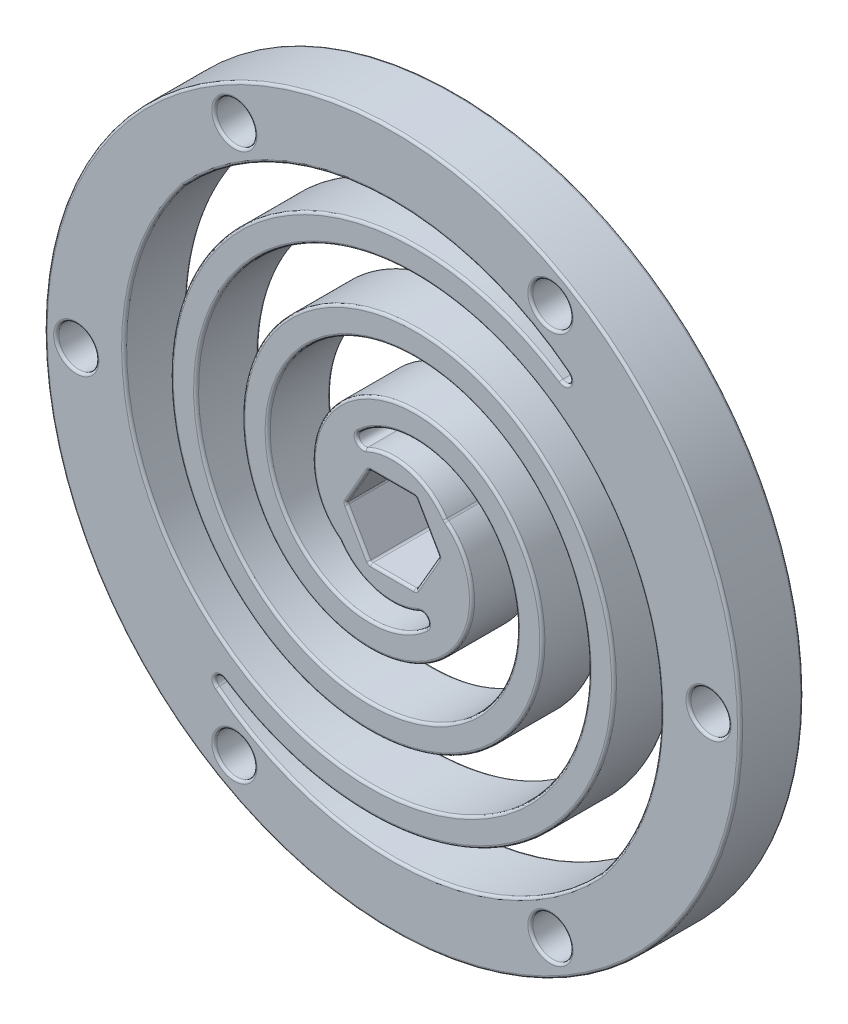
SolidWorks part; units mm, degrees
ref_plane "Front Plane" through (0, 0, 0) normal (0, 0, 1) x (1, 0, 0)
ref_plane "Top Plane" through (0, 0, 0) normal (0, 1, 0) x (1, 0, 0)
ref_plane "Right Plane" through (0, 0, 0) normal (1, 0, 0) x (0, 0, -1)
sketch "Sketch2" plane through (0, 0, 0) normal (0, 0, 1) x (1, 0, 0)
  line L0 (0, 0) -> (27.5, 0) construction
  line L1 (3.6662, 0) -> (1.8331, 3.175)
  line L2 (1.8331, 3.175) -> (-1.8331, 3.175)
  line L3 (-1.8331, 3.175) -> (-3.6662, 0)
  line L4 (-3.6662, 0) -> (-1.8331, -3.175)
  line L5 (-1.8331, -3.175) -> (1.8331, -3.175)
  line L6 (1.8331, -3.175) -> (3.6662, 0)
  line L7 (0, 0) -> (3.6662, 0) construction
  circle A0 centre (0, 0) radius 27.5
  circle A1 centre (0, 0) radius 22.5
  circle A2 centre (0, 0) radius 25 construction
  circle A3 centre (-25, 0) radius 1.5875
  circle A4 centre (0, 0) radius 5
  circle A5 centre (-12.5, 21.6506) radius 1.5875
  circle A6 centre (12.5, 21.6506) radius 1.5875
  circle A7 centre (25, 0) radius 1.5875
  circle A8 centre (12.5, -21.6506) radius 1.5875
  circle A9 centre (-12.5, -21.6506) radius 1.5875
  circle A10 centre (0, 0) radius 3.175 construction
  point P8 (0, 0)
  point P20 (0, 0)
  dimension "D1" = 50
  dimension "D2" = 55
  dimension "D3" = 45
  dimension "D4" = 3.175
  dimension "D5" = 10
  dimension "D7" = 6.35
  dimension "D8" = 0
  dimension "D6" = 6
sketch "Sketch3" plane through (0, 0, 0) normal (0, 0, 1) x (1, 0, 0)
  circle A0 centre (0, 0) radius 5
  circle A1 centre (0, 0) radius 5 construction
curve "Helix/Spiral1"
sketch "Sketch4" plane through (0, 0, 0) normal (0, 0, 1) x (1, 0, 0)
  line L1 (3.6662, 0) -> (1.8331, 3.175)
  line L2 (1.8331, 3.175) -> (-1.8331, 3.175)
  line L3 (-1.8331, 3.175) -> (-3.6662, 0)
  line L4 (-3.6662, 0) -> (-1.8331, -3.175)
  line L5 (-1.8331, -3.175) -> (1.8331, -3.175)
  line L6 (1.8331, -3.175) -> (3.6662, 0)
  circle A0 centre (0, 0) radius 27.5
  circle A1 centre (0, 0) radius 27.5 construction
  arc A2 (21.0974, 7.8198) -> (16.4884, -15.3096) centre (0, 0) ccw
  circle A3 centre (0, 0) radius 22.5 construction
  arc A4 (-4.1867, -2.7335) -> (-4.1828, 2.7394) centre (0, 0) ccw
  circle A5 centre (0, 0) radius 5 construction
  circle A6 centre (0, 0) radius 3.175 construction
  circle A7 centre (-25, 0) radius 1.5875
  circle A8 centre (-25, 0) radius 1.5875 construction
  circle A9 centre (-12.5, 21.6506) radius 1.5875
  circle A10 centre (12.5, 21.6506) radius 1.5875
  circle A11 centre (25, 0) radius 1.5875
  circle A12 centre (12.5, -21.6506) radius 1.5875
  circle A13 centre (-12.5, -21.6506) radius 1.5875
  spline S2 degree 3 poles (-921.9687, 1775.2435) (120.6606, -2.4111) (-4.8813, -17.0729) (-4.2797, 2.414) (-4.1558, 3.0013) (-3.6679, 4.1424) (-3.3002, 4.7041) (-2.3359, 5.6942) (-1.7333, 6.1283) (-0.3515, 6.7692) (0.4351, 6.979) (2.0951, 7.1004) (2.9764, 7.0121) (4.709, 6.5027) (5.5675, 6.0792) (7.1263, 4.9117) (7.8323, 4.163) (8.9643, 2.407) (9.394, 1.3934) (9.878, -0.7846) (9.9334, -1.956) (9.6158, -4.3077) (9.2415, -5.4949) (8.0664, -7.7186) (7.262, -8.761) (5.2882, -10.5401) (4.1135, -11.2809) (1.5171, -12.3274) (0.089, -12.6353) (-2.8511, -12.7334) (-4.3697, -12.5234) (-7.3011, -11.5652) (-8.72, -10.8146) (-11.2595, -8.8244) (-12.3849, -7.5806) (-14.1678, -4.7221) (-14.8283, -3.1019) (-15.559, 0.3326) (-15.6302, 2.1531) (-15.1274, 5.7722) (-14.552, 7.577) (-12.7805, 10.9347) (-11.581, 12.4931) (-8.6672, 15.1438) (-6.9482, 16.24) (-3.1749, 17.7964) (-1.1149, 18.2587) (3.1053, 18.4467) (5.2715, 18.1723) (9.4409, 16.8734) (11.4497, 15.8467) (15.0444, 13.1234) (16.6348, 11.4229) (19.1699, 7.5217) (20.1175, 5.3159) (21.2117, 0.6472) (21.3593, -1.8216) (20.7894, -6.7266) (20.0707, -9.1687) (17.8084, -13.7181) (16.2618, -15.8304) (12.4887, -19.443) (10.2578, -20.9468) (-48.904, -47.2318) (-226.7337, 148.1709) (1422.9512, 1363.8577) knots -1.044974 -1.044974 -1.044974 -1.044974 0.03125 0.03125 0.0625 0.0625 0.09375 0.09375 0.125 0.125 0.15625 0.15625 0.1875 0.1875 0.21875 0.21875 0.25 0.25 0.28125 0.28125 0.3125 0.3125 0.34375 0.34375 0.375 0.375 0.40625 0.40625 0.4375 0.4375 0.46875 0.46875 0.5 0.5 0.53125 0.53125 0.5625 0.5625 0.59375 0.59375 0.625 0.625 0.65625 0.65625 0.6875 0.6875 0.71875 0.71875 0.75 0.75 0.78125 0.78125 0.8125 0.8125 0.84375 0.84375 0.875 0.875 0.90625 0.90625 0.9375 0.9375 0.96875 0.96875 1.691459 1.691459 1.691459 1.691459 only from (-4.0603, 0.3419) to (-0.0726, -24.0026)
  spline S3 degree 3 poles (-4.1828, 2.7394) (-4.1195, 3.0167) (-4.0297, 3.2962) (-3.6679, 4.1424) (-3.3002, 4.7041) (-2.3359, 5.6942) (-1.7333, 6.1283) (-0.3515, 6.7692) (0.4351, 6.979) (2.0951, 7.1004) (2.9764, 7.0121) (4.709, 6.5027) (5.5675, 6.0792) (7.1263, 4.9117) (7.8323, 4.163) (8.9643, 2.407) (9.394, 1.3934) (9.878, -0.7846) (9.9334, -1.956) (9.6158, -4.3077) (9.2415, -5.4949) (8.0664, -7.7186) (7.262, -8.761) (5.2882, -10.5401) (4.1135, -11.2809) (1.5171, -12.3274) (0.089, -12.6353) (-2.8511, -12.7334) (-4.3697, -12.5234) (-7.3011, -11.5652) (-8.72, -10.8146) (-11.2595, -8.8244) (-12.3849, -7.5806) (-14.1678, -4.7221) (-14.8283, -3.1019) (-15.559, 0.3326) (-15.6302, 2.1531) (-15.1274, 5.7722) (-14.552, 7.577) (-12.7805, 10.9347) (-11.581, 12.4931) (-8.6672, 15.1438) (-6.9482, 16.24) (-3.1749, 17.7964) (-1.1149, 18.2587) (3.1053, 18.4467) (5.2715, 18.1723) (9.4409, 16.8734) (11.4497, 15.8467) (15.0444, 13.1234) (16.6348, 11.4229) (19.1699, 7.5217) (20.1175, 5.3159) (21.2117, 0.6472) (21.3593, -1.8216) (20.7894, -6.7266) (20.0707, -9.1687) (18.2649, -12.8) (17.4425, -14.0989) (16.4884, -15.3096) knots 0.047404 0.047404 0.047404 0.047404 0.0625 0.0625 0.09375 0.09375 0.125 0.125 0.15625 0.15625 0.1875 0.1875 0.21875 0.21875 0.25 0.25 0.28125 0.28125 0.3125 0.3125 0.34375 0.34375 0.375 0.375 0.40625 0.40625 0.4375 0.4375 0.46875 0.46875 0.5 0.5 0.53125 0.53125 0.5625 0.5625 0.59375 0.59375 0.625 0.625 0.65625 0.65625 0.6875 0.6875 0.71875 0.71875 0.75 0.75 0.78125 0.78125 0.8125 0.8125 0.84375 0.84375 0.875 0.875 0.90625 0.90625 0.924888 0.924888 0.924888 0.924888
  spline S4 degree 3 poles (-701.7537, 1870.0142) (184.6387, -12.0204) (-7.1764, -26.603) (-6.2709, 2.7296) (-6.093, 3.5576) (-5.4086, 5.1586) (-4.9053, 5.9226) (-3.5964, 7.2666) (-2.7968, 7.8397) (-0.9711, 8.6865) (0.0471, 8.956) (2.1915, 9.1128) (3.3089, 8.9989) (5.5046, 8.3535) (6.5743, 7.8239) (8.5175, 6.3686) (9.3837, 5.4476) (10.7748, 3.2897) (11.2948, 2.0598) (11.882, -0.5833) (11.9472, -1.9883) (11.566, -4.8107) (11.1205, -6.2199) (9.724, -8.8624) (8.7766, -10.0884) (6.4517, -12.1839) (5.08, -13.0477) (2.0459, -14.2706) (0.391, -14.6263) (-3.0198, -14.7401) (-4.7676, -14.4975) (-8.146, -13.3932) (-9.7689, -12.5337) (-12.678, -10.2537) (-13.9577, -8.838) (-15.9889, -5.5815) (-16.7357, -3.7473) (-17.564, 0.1456) (-17.6434, 2.1964) (-17.0761, 6.2794) (-16.4301, 8.3033) (-14.4402, 12.0749) (-13.0998, 13.8152) (-9.8402, 16.7805) (-7.9268, 17.9998) (-3.7216, 19.7344) (-1.4371, 20.2463) (3.2495, 20.4551) (5.6436, 20.1512) (10.2586, 18.7135) (12.4715, 17.5817) (16.438, 14.5767) (18.1847, 12.7081) (20.9739, 8.416) (22.0116, 5.9992) (23.2122, 0.8767) (23.3729, -1.8211) (22.7491, -7.1889) (21.9652, -9.8507) (19.4955, -14.8171) (17.8131, -17.1141) (13.7037, -21.0486) (11.2825, -22.6801) (-52.776, -51.1406) (-239.5534, 161.1192) (1378.94, 1402.9741) knots -1.077999 -1.077999 -1.077999 -1.077999 0.03125 0.03125 0.0625 0.0625 0.09375 0.09375 0.125 0.125 0.15625 0.15625 0.1875 0.1875 0.21875 0.21875 0.25 0.25 0.28125 0.28125 0.3125 0.3125 0.34375 0.34375 0.375 0.375 0.40625 0.40625 0.4375 0.4375 0.46875 0.46875 0.5 0.5 0.53125 0.53125 0.5625 0.5625 0.59375 0.59375 0.625 0.625 0.65625 0.65625 0.6875 0.6875 0.71875 0.71875 0.75 0.75 0.78125 0.78125 0.8125 0.8125 0.84375 0.84375 0.875 0.875 0.90625 0.90625 0.9375 0.9375 0.96875 0.96875 1.688715 1.688715 1.688715 1.688715 only from (-5.9397, -0.3419) to (0.0726, -25.9974)
  spline S5 degree 3 poles (-4.1867, -2.7335) (-5.5181, -1.7681) (-6.3558, -0.0215) (-6.2709, 2.7296) (-6.093, 3.5576) (-5.4086, 5.1586) (-4.9053, 5.9226) (-3.5964, 7.2666) (-2.7968, 7.8397) (-0.9711, 8.6865) (0.0471, 8.956) (2.1915, 9.1128) (3.3089, 8.9989) (5.5046, 8.3535) (6.5743, 7.8239) (8.5175, 6.3686) (9.3837, 5.4476) (10.7748, 3.2897) (11.2948, 2.0598) (11.882, -0.5833) (11.9472, -1.9883) (11.566, -4.8107) (11.1205, -6.2199) (9.724, -8.8624) (8.7766, -10.0884) (6.4517, -12.1839) (5.08, -13.0477) (2.0459, -14.2706) (0.391, -14.6263) (-3.0198, -14.7401) (-4.7676, -14.4975) (-8.146, -13.3932) (-9.7689, -12.5337) (-12.678, -10.2537) (-13.9577, -8.838) (-15.9889, -5.5815) (-16.7357, -3.7473) (-17.564, 0.1456) (-17.6434, 2.1964) (-17.0761, 6.2794) (-16.4301, 8.3033) (-14.4402, 12.0749) (-13.0998, 13.8152) (-9.8402, 16.7805) (-7.9268, 17.9998) (-3.7216, 19.7344) (-1.4371, 20.2463) (3.2495, 20.4551) (5.6436, 20.1512) (10.2586, 18.7135) (12.4715, 17.5817) (16.438, 14.5767) (18.1847, 12.7081) (20.1461, 9.6899) (20.654, 8.7729) (21.0974, 7.8198) knots -0.044468 -0.044468 -0.044468 -0.044468 0.03125 0.03125 0.0625 0.0625 0.09375 0.09375 0.125 0.125 0.15625 0.15625 0.1875 0.1875 0.21875 0.21875 0.25 0.25 0.28125 0.28125 0.3125 0.3125 0.34375 0.34375 0.375 0.375 0.40625 0.40625 0.4375 0.4375 0.46875 0.46875 0.5 0.5 0.53125 0.53125 0.5625 0.5625 0.59375 0.59375 0.625 0.625 0.65625 0.65625 0.6875 0.6875 0.71875 0.71875 0.75 0.75 0.78125 0.78125 0.8125 0.8125 0.825201 0.825201 0.825201 0.825201
  point P24 (42.8445, 11.0919)
  point P25 (0, 0)
  point P26 (0, 0)
  point P37 (0, 0)
  point P38 (0, 0)
  point P43 (-4.608, -2.6817)
  point P45 (0, 0)
  point P46 (0, 0)
  dimension "D2" = 1
  dimension "D3" = 1
  dimension "D1" = 6
extrude "Boss-Extrude1" add sketch "Sketch4" along normal blind 5
pattern_circular "CirPattern1" count 2 over 360 about axis through (0, 0, 5) along (0, 0, -1) of "Boss-Extrude1"
fillet "Fillet1" radius 0.5 6 edges
fillet "Fillet2" radius 0.2 56 edges at (1.8331, 3.175, 2.5) (3.6662, 0, 2.5) (-3.6662, 0, 2.5) (-1.8331, 3.175, 2.5) (1.8331, -3.175, 2.5) (-1.8331, -3.175, 2.5) (-10.9125, -21.6506, 0) (14.0875, -21.6506, 0) (26.5875, 0, 0) (14.0875, 21.6506, 0) (-10.9125, 21.6506, 0) (-23.4125, 0, 0) (27.5, 0, 0) (0, -3.175, 0) (-2.7496, -1.5875, 0) (-2.7496, 1.5875, 0) (0, 3.175, 0) (2.7496, 1.5875, 0) (2.7496, -1.5875, 0) (-10.9125, -21.6506, 5) (26.5875, 0, 5) (-10.9125, 21.6506, 5) (27.5, 0, 5) (-23.4125, 0, 5) (14.0875, 21.6506, 5) (14.0875, -21.6506, 5) (0, 3.175, 5) (-2.7496, 1.5875, 5) (-2.7496, -1.5875, 5) (0, -3.175, 5) (2.7496, -1.5875, 5) (2.7496, 1.5875, 5)
equation "\"t\" = 2mm"
equation "\"b\"= 5mm"
equation "\"rev\"= 1.75"
equation "\"Spring ID\"= 10mm"
equation "\"Bolt Circle Diameter\"= 50mm"
equation "\"D5@Sketch2\"=\"Spring ID\""
equation "\"D1@Sketch2\"=\"Bolt Circle Diameter\""
equation "\"D2@Sketch2\"=\"Bolt Circle Diameter\" + 5"
equation "\"D3@Sketch2\"=\"Bolt Circle Diameter\" - 5"
equation "\"D5@Helix/Spiral1\"=\"rev\""
equation "\"Pitch\"= ( \"Bolt Circle Diameter\" - \"Spring ID\" ) / ( 2 * \"rev\" )"
equation "\"D2@Sketch4\"=\"t\"/2"
equation "\"D3@Sketch4\"=\"t\"/2"
equation "\"D1@Boss-Extrude1\"=\"b\""
equation "\"D4@Helix/Spiral1\"=\"Pitch\""
